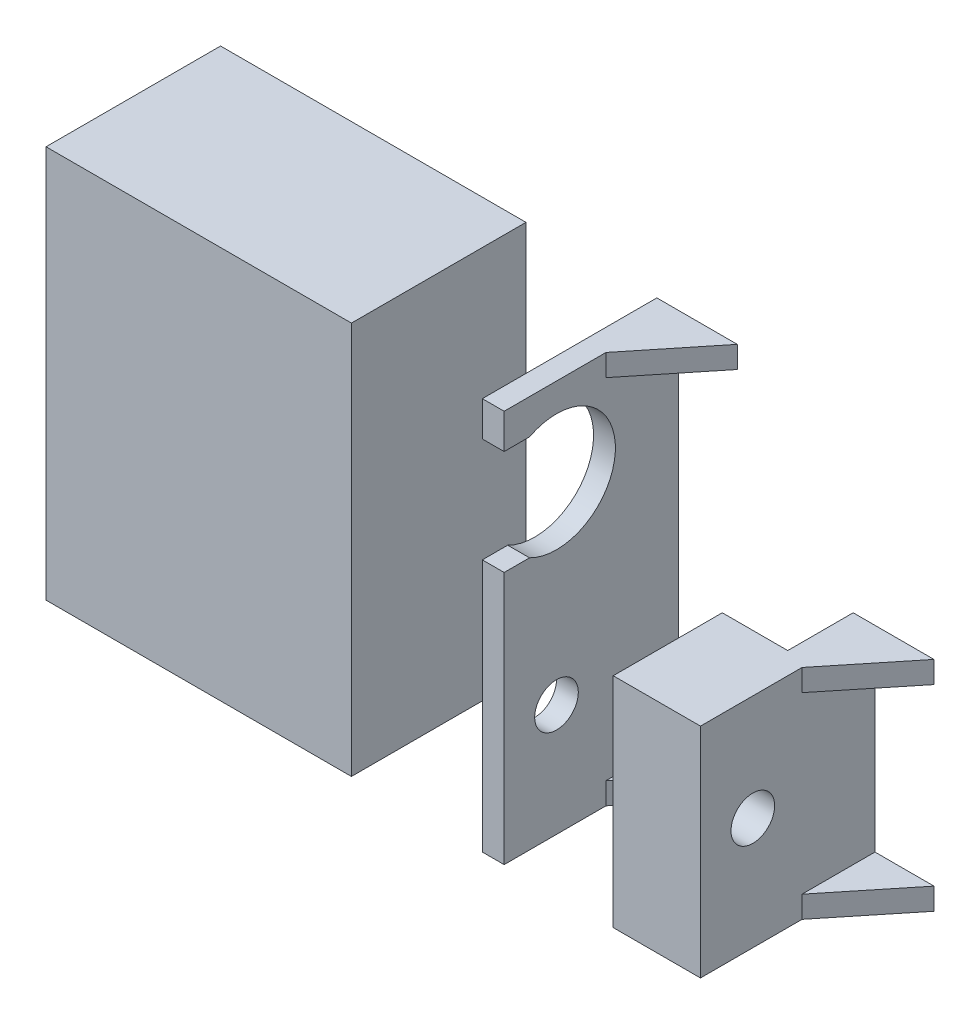
SolidWorks part; units mm, degrees
ref_plane "Front Plane" through (0, 0, 0) normal (0, 0, 1) x (1, 0, 0)
ref_plane "Top Plane" through (0, 0, 0) normal (0, 1, 0) x (1, 0, 0)
ref_plane "Right Plane" through (0, 0, 0) normal (1, 0, 0) x (0, 0, -1)
sketch "Sketch1" plane through (0, 0, 0) normal (0, 0, 1) x (1, 0, 0)
  line L1 (-150, 100) -> (150, 100)
  line L2 (-150, 100) -> (-150, -100)
  line L3 (-150, -100) -> (150, -100)
  line L4 (150, 100) -> (150, -100)
  line L5 (-150, 100) -> (150, -100) construction
  line L6 (-150, -100) -> (150, 100) construction
  point P0 (0, 0)
  dimension "D1" = 300
  dimension "D2" = 200
extrude "Boss-Extrude1" add sketch "Sketch1" along normal blind 5
sketch "Sketch3" plane through (0, 0, 5) normal (0, 0, 1) x (1, 0, 0)
  line L1 (-150, -100) -> (-130, -100)
  line L2 (-150, -100) -> (-150, -80)
  line L3 (-150, -80) -> (-130, -80)
  line L4 (-130, -100) -> (-130, -80)
  line L5 (-150, 100) -> (-130, 100)
  line L6 (-150, 100) -> (-150, 60)
  line L7 (-150, 60) -> (-130, 60)
  line L8 (-130, 100) -> (-130, 60)
  line L9 (150, 100) -> (130, 100)
  line L10 (150, 100) -> (150, 60)
  line L11 (150, 60) -> (130, 60)
  line L12 (130, 100) -> (130, 60)
  line L13 (150, -100) -> (130, -100)
  line L14 (150, -100) -> (150, -80)
  line L15 (150, -80) -> (130, -80)
  line L16 (130, -100) -> (130, -80)
  dimension "D1" = 20
  dimension "D2" = 20
  dimension "D3" = 40
extrude "Cut-Extrude1" cut sketch "Sketch3" against normal blind 5
sketch "Sketch4" plane through (0, 0, 0) normal (0, 0, -1) x (-1, 0, 0)
  line L0 (-150, -80) -> (-150, 60) construction
  line L1 (-130, -100) -> (-150, -100)
  line L2 (-130, -100) -> (-130, -60)
  line L3 (-130, -60) -> (-150, -60)
  line L4 (-150, -100) -> (-150, -60)
  line L5 (150, 60) -> (150, -80) construction
  line L6 (130, -100) -> (150, -100)
  line L7 (130, -100) -> (130, -60)
  line L8 (130, -60) -> (150, -60)
  line L9 (150, -100) -> (150, -60)
  dimension "D1" = 40
  dimension "D2" = 40
extrude "Cut-Extrude2" cut sketch "Sketch4" against normal blind 10
sketch "Sketch6" plane through (0, 0, 0) normal (0, 0, -1) x (-1, 0, 0)
  line L0 (150, 60) -> (150, -60) construction
  line L1 (-150, 100) -> (150, 100)
  line L2 (-150, 100) -> (-150, -100)
  line L3 (-150, -100) -> (150, -100)
  line L4 (150, 100) -> (150, -100)
  line L5 (130, -100) -> (-130, -100) construction
  line L6 (-130, 100) -> (130, 100) construction
  line L7 (-150, -60) -> (-150, 60) construction
extrude "Boss-Extrude2" add sketch "Sketch6" against normal blind 5
sketch "Sketch8" plane through (0, 0, 5) normal (0, 0, 1) x (1, 0, 0)
  line L0 (150, 100) -> (-150, 100) construction
  line L1 (-100, 20) -> (-95, 20)
  line L2 (-100, 20) -> (-100, -20)
  line L4 (-95, 20) -> (-95, -20)
  line L5 (-150, 100) -> (-150, -100) construction
  line L6 (-150, -100) -> (150, -100) construction
  line L7 (55, 20) -> (60, 20)
  line L8 (55, 20) -> (55, -20)
  line L9 (55, -20) -> (60, -20)
  line L10 (60, 20) -> (60, -20)
  line L12 (-100, -20) -> (-100, -70)
  line L13 (-100, -70) -> (-95, -70)
  line L14 (-95, -20) -> (-95, -70)
  dimension "D1" = 5
  dimension "D3" = 80
  dimension "D4" = 50
  dimension "D5" = 150
  dimension "D6" = 30
extrude "Boss-Extrude4" add sketch "Sketch8" along normal blind 40 contours L12 L13 L14 L4 L1 L2
extrude "Boss-Extrude5" add sketch "Sketch8<3>" along normal blind 40 contours L8 L9 L10 L7
sketch "Sketch8<3>" plane through (0, 0, 5) normal (0, 0, 1) x (1, 0, 0) same geometry as "Sketch8"
sketch "Sketch9" plane through (60, 0, 0) normal (1, 0, 0) x (0, 0, -1)
  line L0 (-45, 20) -> (-45, -20) construction
  line L1 (-45, 12) -> (-33, 12)
  line L2 (-45, 12) -> (-45, -12)
  line L3 (-45, -12) -> (-33, -12)
  line L5 (-45, -20) -> (-5, -20) construction
  arc A0 (-33, -12) -> (-33, 12) centre (-33, 0) ccw
  dimension "D3" = 24
  dimension "D1" = 24
  dimension "D2" = 8
extrude "Cut-Extrude3" cut sketch "Sketch9" against normal blind 236
sketch "Sketch10" plane through (-95, 0, 0) normal (1, 0, 0) x (0, 0, -1)
  circle A0 centre (-33, -44.2799) radius 5
  dimension "D1" = 10
extrude "Cut-Extrude4" cut sketch "Sketch10" against normal blind 236 contours A0
sketch "Sketch11" plane through (0, -70, 0) normal (0, -1, 0) x (1, 0, 0)
  line L0 (-95, 21.6604) -> (-81.5668, 5)
  line L1 (-95, 45) -> (-95, 5) construction
  line L2 (-150, 5) -> (150, 5) construction
  line L3 (-81.5668, 5) -> (-95, 5)
  line L4 (-95, 5) -> (-95, 21.6604)
  line L5 (60, 21.6604) -> (72.769, 5)
  line L6 (60, 45) -> (60, 5) construction
  line L7 (72.769, 5) -> (60, 5)
  line L8 (60, 5) -> (60, 21.6604)
extrude "Boss-Extrude6" add sketch "Sketch11" against normal blind 5 contours L0 L3 L4
sketch "Sketch12" plane through (0, 20, 0) normal (0, 1, 0) x (1, 0, 0)
  line L0 (-81.5668, -5) -> (-95, -21.6604)
  line L1 (-95, -21.6604) -> (-95, -5)
  line L2 (-95, -5) -> (-81.5668, -5)
  line L3 (60, -21) -> (73.767, -5)
  line L4 (150, -5) -> (-150, -5) construction
  line L5 (73.767, -5) -> (60, -5)
  line L6 (60, -5) -> (60, -21)
extrude "Boss-Extrude7" add sketch "Sketch12" against normal blind 5 contours L3 L5 L6
extrude "Boss-Extrude8" add sketch "Sketch12<3>" against normal blind 5 contours L0 L1 L2
sketch "Sketch12<3>" plane through (0, 20, 0) normal (0, 1, 0) x (1, 0, 0) same geometry as "Sketch12"
ref_plane "Plane1" through (0, 0, 0) normal (0, -1, 0) x (-1, 0, 0)
mirror "Mirror1" about plane through (0, 0, 0) normal (0, -1, 0) of "Boss-Extrude7"
ref_plane "Plane3" through (-75, 0, 0) normal (1, 0, 0) x (0, 0, -1)
mirror "Mirror3" about plane through (-75, 0, 0) normal (1, 0, 0) of "Cut-Extrude4", "Boss-Extrude4"
sketch "Sketch17" plane through (-55, 0, 0) normal (-1, 0, 0) x (0, 0, 1)
  line L0 (5, -20) -> (45, -20)
  line L1 (5, 20) -> (45, 20)
  line L2 (5, 20) -> (5, -20)
  line L4 (45, 20) -> (45, -12)
  line L5 (45, 20) -> (45, -70) construction
  line L6 (45, -20) -> (45, -12)
  dimension "D1" = 40
extrude "Cut-Extrude5" cut sketch "Sketch17" against normal blind 10
sketch "Sketch19" plane through (-55, 0, 0) normal (-1, 0, 0) x (0, 0, 1)
  line L0 (45, -70) -> (5, -70) construction
  line L1 (45, -20) -> (20, -20)
  line L2 (45, -20) -> (45, -70)
  line L3 (45, -70) -> (20, -70)
  line L4 (20, -20) -> (20, -70)
  dimension "D1" = 25
extrude "Boss-Extrude10" add sketch "Sketch19" along normal blind 15
sketch "Sketch20" plane through (0, -70, 0) normal (0, -1, 0) x (1, 0, 0)
  line L0 (-50, 21.718) -> (-36.4832, 5)
  line L1 (-50, 45) -> (-50, 5) construction
  line L2 (-36.4832, 5) -> (-50, 5)
  line L3 (-50, 5) -> (-50, 21.718)
extrude "Boss-Extrude11" add sketch "Sketch20" against normal blind 5
ref_plane "Plane4" through (0, -45, 0) normal (0, 1, 0) x (1, 0, 0)
mirror "Mirror4" about plane through (0, -45, 0) normal (0, 1, 0) of "Boss-Extrude11"
sketch "Sketch22" plane through (-75, 0, 0) normal (1, 0, 0) x (0, 0, -1)
  circle A0 centre (-33, -44.2799) radius 5
extrude "Cut-Extrude6" cut sketch "Sketch22" along normal blind 39
sketch "Sketch23" plane through (-100, 0, 0) normal (-1, 0, 0) x (0, 0, 1)
  circle A0 centre (33, 0) radius 13.5
  dimension "D1" = 27
extrude "Cut-Extrude7" cut sketch "Sketch23" against normal blind 10
sketch "Sketch25" plane through (0, 0, 5) normal (0, 0, 1) x (1, 0, 0)
  line L1 (-100, 20) -> (-36.4832, 20)
  line L2 (-100, 20) -> (-100, -70)
  line L3 (-100, -70) -> (-36.4832, -70)
  line L4 (-36.4832, 20) -> (-36.4832, -70)
  line L5 (-150, 100) -> (150, 100)
  line L6 (-150, 100) -> (-150, -100)
  line L7 (-150, -100) -> (150, -100)
  line L8 (150, 100) -> (150, -100)
extrude "Cut-Extrude8" cut sketch "Sketch25" along normal blind 195
extrude "Cut-Extrude9" cut sketch "Sketch25<2>" against normal blind 195 contours L5 L8 L7 L6
sketch "Sketch25<2>" plane through (0, 0, 5) normal (0, 0, 1) x (1, 0, 0) same geometry as "Sketch25"
ref_plane "Plane5" through (-130, 0, 0) normal (-1, 0, 0) x (0, 0, 1)
sketch "Sketch26" plane through (-130, 0, 0) normal (-1, 0, 0) x (0, 0, 1)
  line L0 (45, 20) -> (45, -70)
  line L1 (5, 20) -> (45, 20)
  line L2 (5, 20) -> (5, -70)
  line L3 (5, -70) -> (45, -70)
  dimension "D1" = 40
  dimension "D2" = 40
extrude "Boss-Extrude12" add sketch "Sketch26" along normal blind 70 separate body
